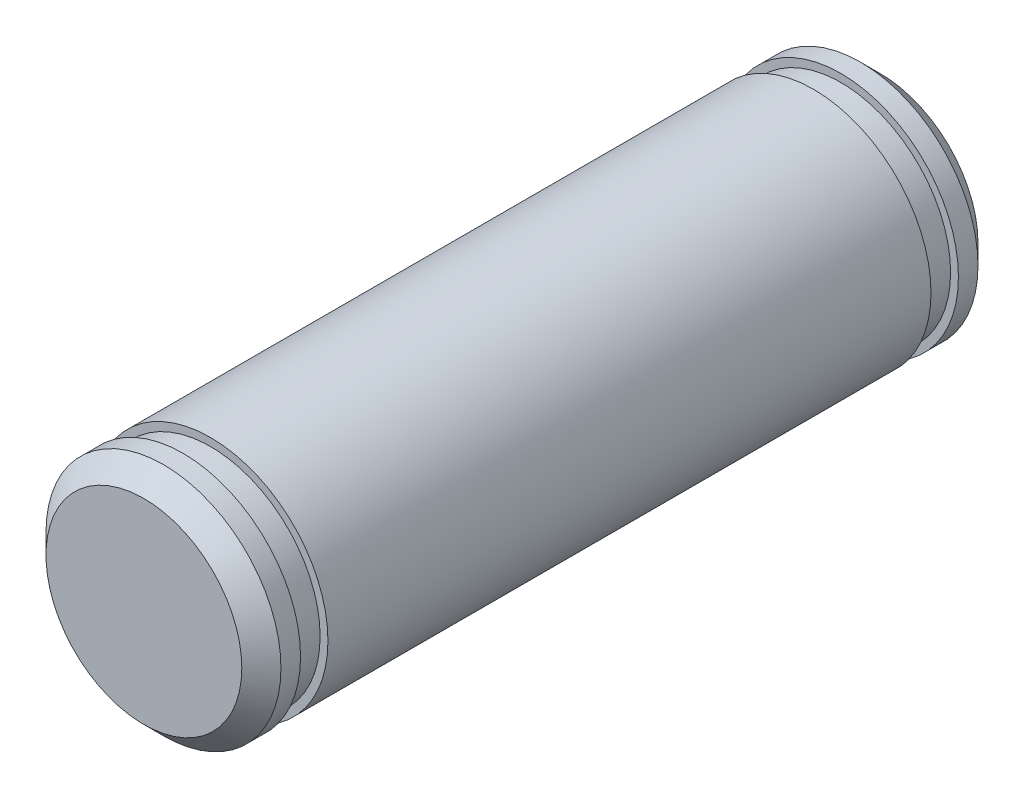
SolidWorks part; units mm, degrees
material "Chromowa stal nierdzewna"
ref_plane "Płaszczyzna przednia" through (0, 0, 0) normal (0, 0, 1) x (1, 0, 0)
ref_plane "Płaszczyzna górna" through (0, 0, 0) normal (0, 1, 0) x (1, 0, 0)
ref_plane "Płaszczyzna prawa" through (0, 0, 0) normal (1, 0, 0) x (0, 0, -1)
sketch "Szkic1" plane through (0, 0, 0) normal (0, 0, 1) x (1, 0, 0)
  circle A0 centre (0, 0) radius 3
  dimension "D1" = 6
extrude "Dodanie-wyciągnięcie1" add sketch "Szkic1" along normal blind 18.8
sketch "Szkic2" plane through (0, 0, 18.8) normal (0, 0, 1) x (1, 0, 0)
  circle A0 centre (0, 0) radius 3
  circle A1 centre (0, 0) radius 2.8
  dimension "D1" = 6
  dimension "D2" = 5.6
extrude "Wytnij-wyciągnięcie1" cut sketch "Szkic2" against normal blind 0.7 from offset 1 offset against normal yes
extrude "Wytnij-wyciągnięcie2" cut sketch "Szkic2<2>" along normal blind 0.7 from offset 17.8 offset against normal yes
sketch "Szkic2<2>" plane through (0, 0, 18.8) normal (0, 0, 1) x (1, 0, 0) same geometry as "Szkic2"
chamfer "Sfazowanie1" distance 0.5 angle 45 2 edges at (3, 0, 0) (3, 0, 18.8)
